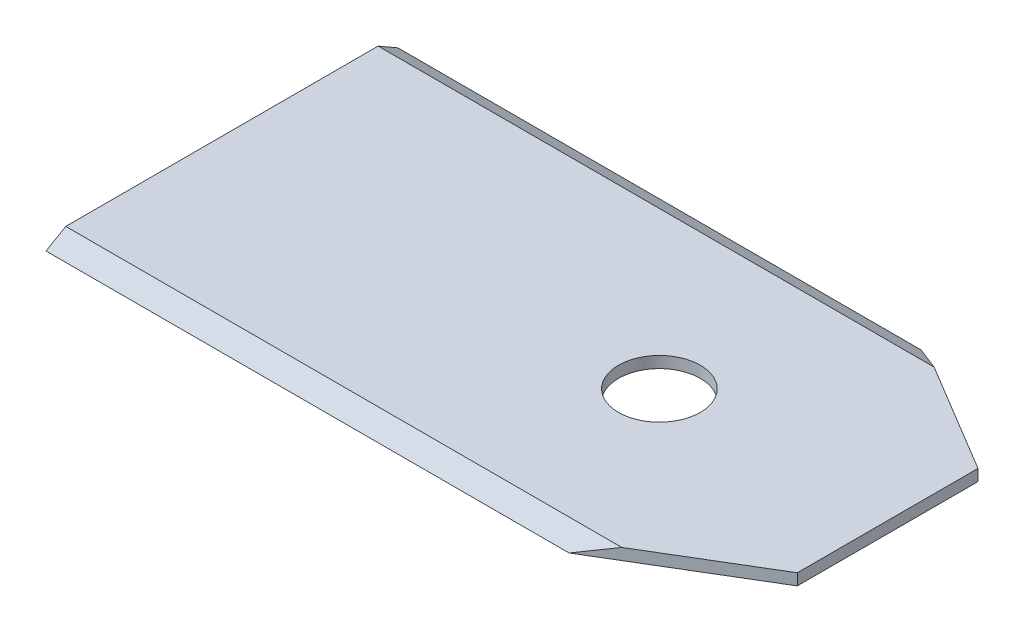
SolidWorks part; units mm, degrees
ref_plane "Plan de face" through (0, 0, 0) normal (0, 0, 1) x (1, 0, 0)
ref_plane "Plan de dessus" through (0, 0, 0) normal (0, 1, 0) x (1, 0, 0)
ref_plane "Plan de droite" through (0, 0, 0) normal (1, 0, 0) x (0, 0, -1)
sketch "Esquisse1" plane through (0, 0, 0) normal (0, 1, 0) x (1, 0, 0)
  line L0 (-19.9159, 0) -> (15.815, 0) construction
  line L1 (27.5, 9.25) -> (35, 4.75)
  line L2 (27.5, -9.25) -> (0, -9.25)
  line L3 (35, -4.75) -> (35, 4.75)
  line L4 (27.5, 9.25) -> (0, 9.25)
  line L5 (0, -9.25) -> (0, 9.25)
  line L6 (11.6251, -18.775) -> (0, 9.25) construction
  line L7 (11.6251, 18.775) -> (0, -9.25) construction
  line L8 (27.5, -9.25) -> (35, -4.75)
  point P3 (3.837, 0)
  dimension "D1" = 7.5
  dimension "D2" = 18.5
  dimension "D3" = 4.5
  dimension "D4" = 35
extrude "Boss.-Extru.1" add sketch "Esquisse1" along normal blind 0.6
hole_wizard "Dégagement M41" positions "Esquisse4" profile "Esquisse5" hole size "M4" standard "ISO" end condition through all
sketch "Esquisse4" plane through (0, 0.6, 0) normal (0, 1, 0) x (1, 0, 0)
  line L0 (-4.0311, 0) -> (45.0383, 0) construction
  line L3 (35, -4.75) -> (35, 4.75) construction
  point P0 (23, 0)
  dimension "D1" = 12
sketch "Esquisse5" plane through (23, 0.6, 0) normal (1, 0, 0) x (0, 0, 1)
  line L0 (0, 0) -> (0, 0.6)
  line L1 (0, 0.6) -> (2.15, 0.6)
  line L2 (2.15, 0.6) -> (2.15, 0)
  line L5 (2.15, 0) -> (0, 0)
  line L11 (0, -6.35) -> (0, 107.95) construction
  dimension "Diamètre du perçage jusqu'au prochain" = 4.3
  dimension "Profondeur du perçage jusqu'au prochain" = 0.6
chamfer "Chanfrein1" distance 0.6 angle 60 2 edges at (13.75, 0.6, -9.25) (13.75, 0.6, 9.25) first distance on face at (13.75, 0.3, -9.25) first distance on face at (13.75, 0.3, 9.25)
